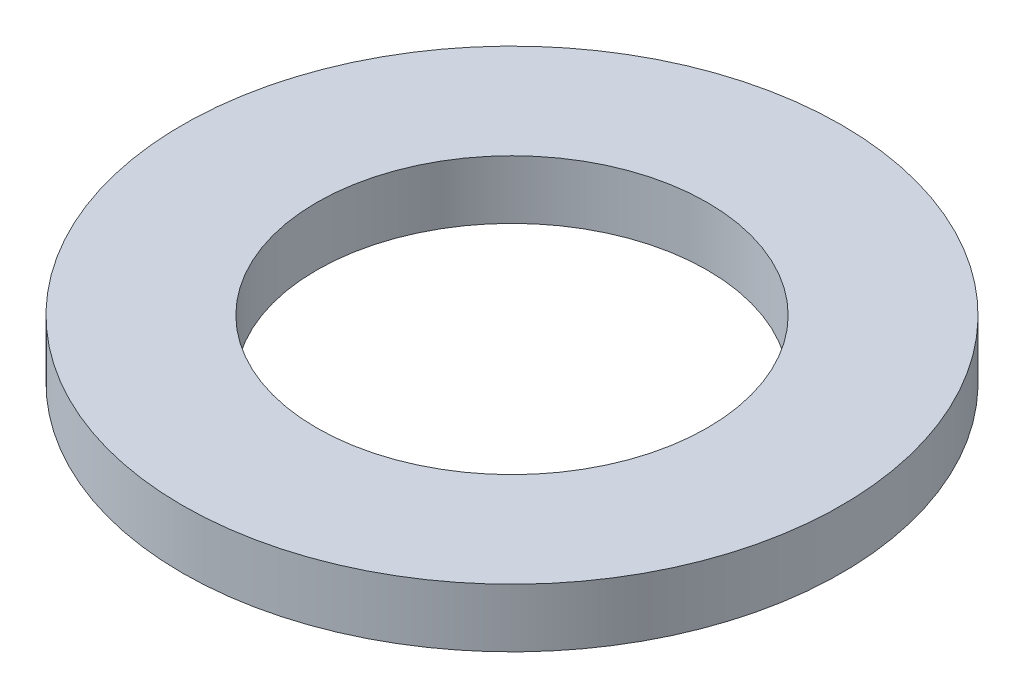
SolidWorks part; units mm, degrees
ref_plane "Front Plane" through (0, 0, 0) normal (0, 0, 1) x (1, 0, 0)
ref_plane "Top Plane" through (0, 0, 0) normal (0, 1, 0) x (1, 0, 0)
ref_plane "Right Plane" through (0, 0, 0) normal (1, 0, 0) x (0, 0, -1)
sketch "Sketch1" plane through (0, 0, 0) normal (0, 1, 0) x (1, 0, 0)
  circle A0 centre (0, 0) radius 67.5
  dimension "FLANGE_OD" = 135
extrude "Boss-Extrude1" add sketch "Sketch1" along normal blind 12
sketch "Sketch2" plane through (0, 0, 0) normal (0, 1, 0) x (1, 0, 0)
  circle A0 centre (0, 0) radius 40
  dimension "BORE_D" = 80
extrude "Cut-Extrude1" cut sketch "Sketch2" along normal through all
sketch "Sketch3" plane through (0, 12, 0) normal (0, 1, 0) x (1, 0, 0)
  circle A0 centre (0, 0) radius 27.7523 construction
  circle A1 centre (-27.7523, 0) radius 3.6645
  dimension "BOLT_D" = 7.329
  dimension "BOLT_PCD" = 55.5045
extrude "Cut-Extrude2" cut sketch "Sketch3" against normal blind 11.854 rebuild error yes
pattern_circular "CirPattern1" count 8 over 360 rebuild error yes
